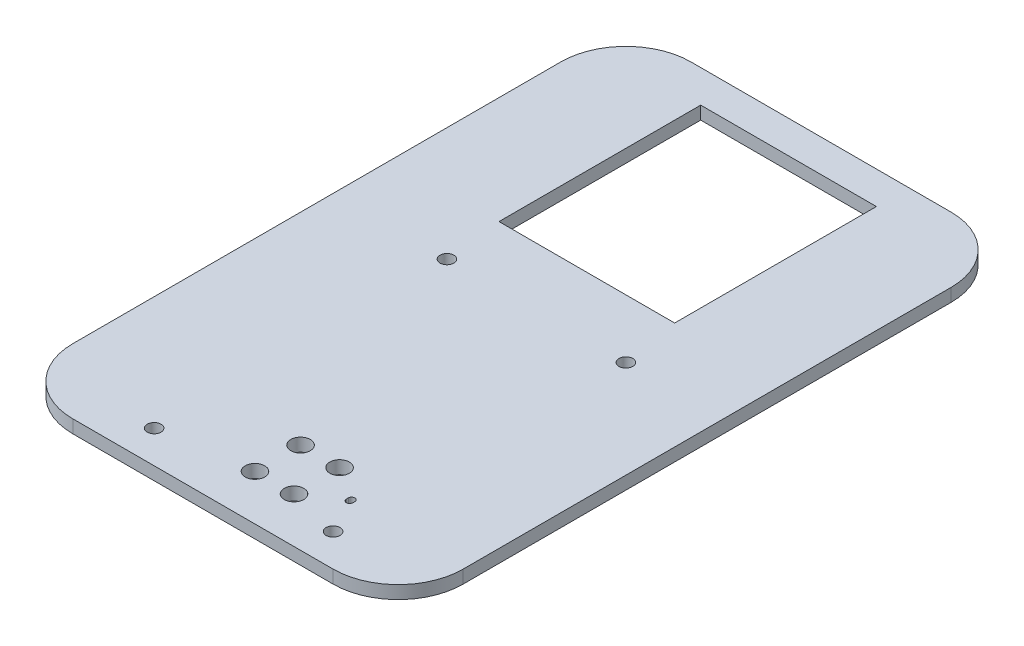
SolidWorks part; units mm, degrees
ref_plane "Front Plane" through (0, 0, 0) normal (0, 0, 1) x (1, 0, 0)
ref_plane "Top Plane" through (0, 0, 0) normal (0, 1, 0) x (1, 0, 0)
ref_plane "Right Plane" through (0, 0, 0) normal (1, 0, 0) x (0, 0, -1)
sketch "Sketch2" plane through (0, 0, 0) normal (0, 1, 0) x (1, 0, 0)
  line L0 (-25.4, -60.325) -> (25.4, -60.325)
  line L1 (-38.1, -47.625) -> (-38.1, 47.625)
  line L2 (38.1, -47.625) -> (38.1, 47.625)
  line L3 (-25.4, 60.325) -> (25.4, 60.325)
  line L4 (-38.1, -60.325) -> (38.1, 60.325) construction
  line L5 (38.1, -60.325) -> (-38.1, 60.325) construction
  arc A0 (-38.1, 47.625) -> (-25.4, 60.325) centre (-25.4, 47.625) cw
  arc A1 (38.1, 47.625) -> (25.4, 60.325) centre (25.4, 47.625) ccw
  arc A2 (25.4, -60.325) -> (38.1, -47.625) centre (25.4, -47.625) ccw
  arc A3 (-38.1, -47.625) -> (-25.4, -60.325) centre (-25.4, -47.625) ccw
  dimension "D3" = 12.7
  dimension "D4" = 12.7
  dimension "D1" = 120.65
  dimension "D2" = 76.2
extrude "top" add sketch "Sketch2" along normal blind 2.54
sketch "PCBOutline" plane through (0, 2.54, 2.54) normal (0, 1, 0) x (1, 0, 0)
  line L0 (-25.4, -57.785) -> (25.4, -57.785) construction
  line L1 (-19.05, -55.245) -> (22.86, -55.245)
  line L2 (-19.05, -55.245) -> (-19.05, 9.525)
  line L3 (-19.05, 9.525) -> (22.86, 9.525)
  line L4 (22.86, -55.245) -> (22.86, 9.525)
  line L5 (-38.1, 50.165) -> (-38.1, -45.085) construction
  dimension "D1" = 41.91
  dimension "D2" = 64.77
  dimension "D3" = 2.54
  dimension "D4" = 19.05
sketch "Sketch7" plane through (0, 2.54, 0) normal (0, 1, 0) x (1, 0, 0)
  line L1 (1.27, -51.435) -> (8.89, -51.435) construction
  line L2 (1.27, -51.435) -> (1.27, -42.545) construction
  line L3 (-19.05, -57.785) -> (-19.05, 6.985) construction
  line L4 (15.494, -46.7995) -> (15.494, -47.1805) construction
  line L5 (16.129, -46.7995) -> (16.129, -47.1805)
  line L6 (14.859, -46.7995) -> (14.859, -47.1805)
  line L7 (1.27, -46.99) -> (15.494, -46.99) construction
  line L8 (-19.05, -57.785) -> (22.86, -57.785) construction
  circle A0 centre (1.27, -51.435) radius 1.905
  circle A1 centre (8.89, -51.435) radius 1.905
  circle A2 centre (8.89, -42.545) radius 1.905
  circle A3 centre (1.27, -42.545) radius 1.905
  arc A4 (16.129, -46.7995) -> (14.859, -46.7995) centre (15.494, -46.7995) ccw
  arc A5 (14.859, -47.1805) -> (16.129, -47.1805) centre (15.494, -47.1805) ccw
  point P6 (15.494, -46.99)
  dimension "D7" = 3.81
  dimension "D4" = 7.62
  dimension "D5" = 8.89
  dimension "D6" = 20.32
  dimension "D8" = 14.224
  dimension "D9" = 0.381
  dimension "D10" = 1.27
  dimension "D11" = 6.35
  dimension "D2" = 2
  dimension "D3" = 2
extrude "ButtonLEDCut" cut sketch "Sketch7" against normal through all
sketch "Sketch8" plane through (0, 2.54, 0) normal (0, 1, 0) x (1, 0, 0)
  line L0 (0, 0) -> (0, 60.325) construction
  line L1 (25.4, 60.325) -> (-25.4, 60.325) construction
  line L2 (-17.145, 14.605) -> (-17.145, 53.975)
  line L3 (-17.145, 14.605) -> (17.145, 14.605)
  line L4 (-17.145, 53.975) -> (17.145, 53.975)
  line L5 (17.145, 14.605) -> (17.145, 53.975)
  line L6 (-17.145, 14.605) -> (17.145, 53.975) construction
  line L7 (-17.145, 53.975) -> (17.145, 14.605) construction
  line L8 (-17.145, 19.685) -> (17.145, 19.685) construction
  point P6 (0, 34.29)
  dimension "D1" = 6.35
  dimension "D2" = 34.29
  dimension "D3" = 34.29
  dimension "D4" = 39.37
extrude "SolarCut" cut sketch "Sketch8" against normal through all
sketch "Mounting Holes" plane through (0, 2.54, 2.54) normal (0, 1, 0) x (1, 0, 0)
  line L2 (-19.05, -55.245) -> (-19.05, 9.525) construction
  line L3 (-19.05, -55.245) -> (22.86, -55.245) construction
  point P0 (-15.875, 5.715)
  point P2 (19.05, 5.715)
  point P4 (19.05, -51.435)
  point P6 (-15.875, -51.435)
  dimension "D1" = 3.175
  dimension "D2" = 3.81
  dimension "D3" = 34.925
  dimension "D4" = 57.15
hole_wizard "#6-32 Tapped Hole1" positions "Sketch12" profile "Sketch11" tap size "#6-32" standard "ANSI Inch"
sketch "Sketch12" plane through (0, 2.54, 0) normal (0, 1, 0) x (1, 0, 0)
  point P0 (-15.875, 3.175)
  point P3 (19.05, 3.175)
  point P6 (19.05, -53.975)
  point P9 (-15.875, -53.975)
sketch "Sketch11" plane through (-15.875, 2.54, -3.175) normal (1, 0, 0) x (0, 0, 1)
  line L0 (0, 0) -> (0, 11.9887)
  line L1 (0, 11.9887) -> (1.3525, 11.176)
  line L2 (1.3525, 11.176) -> (1.3525, 0)
  line L5 (1.3525, 0) -> (0, 0)
  line L10 (0, 11.9887) -> (-1.3526, 11.176) construction
  line L11 (0, -6.35) -> (0, 107.95) construction
  dimension "Tap Drill Dia." = 2.7051
  dimension "Tap Drill Depth" = 11.176
  dimension "Drill Angle" = 118
